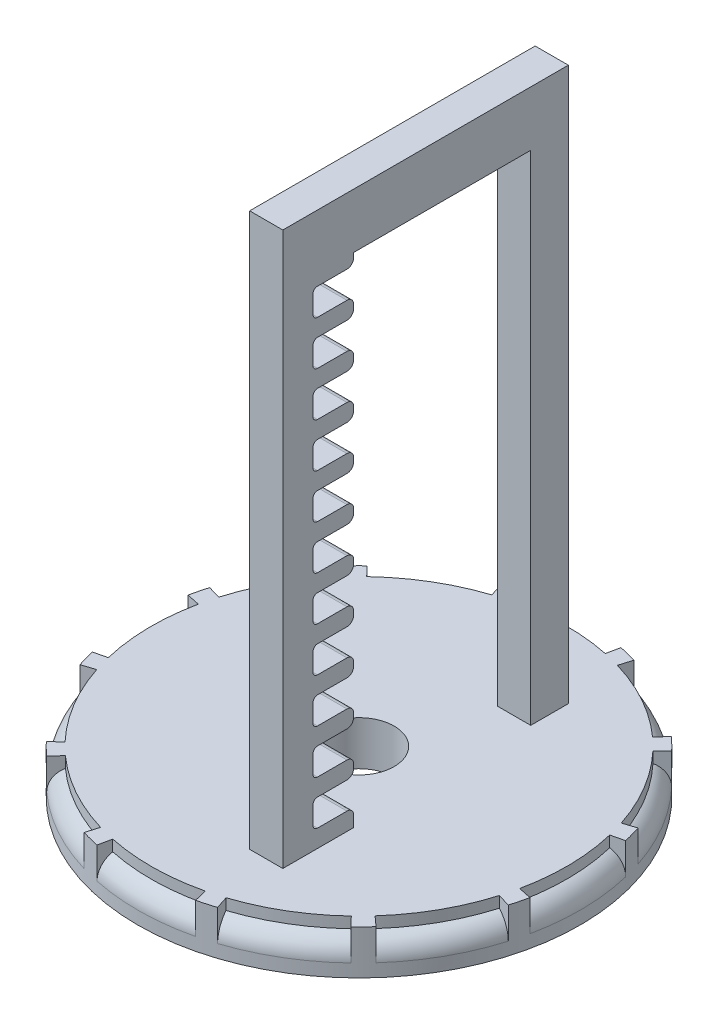
SolidWorks part; units mm, degrees
ref_plane "Front Plane" through (0, 0, 0) normal (0, 0, 1) x (1, 0, 0)
ref_plane "Top Plane" through (0, 0, 0) normal (0, 1, 0) x (1, 0, 0)
ref_plane "Right Plane" through (0, 0, 0) normal (1, 0, 0) x (0, 0, -1)
sketch "Sketch1" plane through (0, 0, 0) normal (0, 1, 0) x (1, 0, 0)
  circle A0 centre (0, 0) radius 100
  dimension "D1" = 200
extrude "Boss-Extrude1" add sketch "Sketch1" along normal blind 20
sketch "Sketch2" plane through (0, 20, 0) normal (0, 1, 0) x (1, 0, 0)
  line L0 (-23.3506, 97.2355) -> (-21.9496, 91.4014)
  line L2 (-1.4202, 99.9972) -> (0, 0) construction
  line L3 (19.345, 91.9879) -> (20.5798, 97.8594)
  line L4 (28.3956, 95.8837) -> (26.6918, 90.1307)
  line L5 (62.7472, 69.9913) -> (66.7524, 74.4589)
  line L6 (72.5331, 68.84) -> (68.1812, 64.7096)
  line L7 (89.3364, 29.2406) -> (95.0387, 31.1071)
  line L8 (97.2355, 23.3506) -> (91.4014, 21.9496)
  line L9 (91.9879, -19.345) -> (97.8594, -20.5798)
  line L10 (95.8837, -28.3956) -> (90.1307, -26.6918)
  line L11 (69.9913, -62.7472) -> (74.4589, -66.7524)
  line L12 (68.84, -72.5331) -> (64.7096, -68.1812)
  line L13 (29.2406, -89.3364) -> (31.1071, -95.0387)
  line L14 (23.3506, -97.2355) -> (21.9496, -91.4014)
  line L15 (-19.345, -91.9879) -> (-20.5798, -97.8594)
  line L16 (-28.3956, -95.8837) -> (-26.6918, -90.1307)
  line L17 (-62.7472, -69.9913) -> (-66.7524, -74.4589)
  line L18 (-72.5331, -68.84) -> (-68.1812, -64.7096)
  line L19 (-89.3364, -29.2406) -> (-95.0387, -31.1071)
  line L20 (-97.2355, -23.3506) -> (-91.4014, -21.9496)
  line L21 (-91.9879, 19.345) -> (-97.8594, 20.5798)
  line L22 (-95.8837, 28.3956) -> (-90.1307, 26.6918)
  line L23 (-69.9913, 62.7472) -> (-74.4589, 66.7524)
  line L24 (-68.84, 72.5331) -> (-64.7096, 68.1812)
  line L25 (-29.2406, 89.3364) -> (-31.1071, 95.0387)
  line L26 (0, 0) -> (-1.3349, 93.9905) construction
  circle A0 centre (0, 0) radius 100 construction
  arc A1 (-21.9496, 91.4014) -> (19.345, 91.9879) centre (0, 0) cw
  arc A3 (-23.3506, 97.2355) -> (20.5798, 97.8594) centre (0, 0) cw
  arc A4 (28.3956, 95.8837) -> (66.7524, 74.4589) centre (0, 0) cw
  arc A5 (26.6918, 90.1307) -> (62.7472, 69.9913) centre (0, 0) cw
  arc A6 (72.5331, 68.84) -> (95.0387, 31.1071) centre (0, 0) cw
  arc A7 (68.1812, 64.7096) -> (89.3364, 29.2406) centre (0, 0) cw
  arc A8 (97.2355, 23.3506) -> (97.8594, -20.5798) centre (0, 0) cw
  arc A9 (91.4014, 21.9496) -> (91.9879, -19.345) centre (0, 0) cw
  arc A10 (95.8837, -28.3956) -> (74.4589, -66.7524) centre (0, 0) cw
  arc A11 (90.1307, -26.6918) -> (69.9913, -62.7472) centre (0, 0) cw
  arc A12 (68.84, -72.5331) -> (31.1071, -95.0387) centre (0, 0) cw
  arc A13 (64.7096, -68.1812) -> (29.2406, -89.3364) centre (0, 0) cw
  arc A14 (23.3506, -97.2355) -> (-20.5798, -97.8594) centre (0, 0) cw
  arc A15 (21.9496, -91.4014) -> (-19.345, -91.9879) centre (0, 0) cw
  arc A16 (-28.3956, -95.8837) -> (-66.7524, -74.4589) centre (0, 0) cw
  arc A17 (-26.6918, -90.1307) -> (-62.7472, -69.9913) centre (0, 0) cw
  arc A18 (-72.5331, -68.84) -> (-95.0387, -31.1071) centre (0, 0) cw
  arc A19 (-68.1812, -64.7096) -> (-89.3364, -29.2406) centre (0, 0) cw
  arc A20 (-97.2355, -23.3506) -> (-97.8594, 20.5798) centre (0, 0) cw
  arc A21 (-91.4014, -21.9496) -> (-91.9879, 19.345) centre (0, 0) cw
  arc A22 (-95.8837, 28.3956) -> (-74.4589, 66.7524) centre (0, 0) cw
  arc A23 (-90.1307, 26.6918) -> (-69.9913, 62.7472) centre (0, 0) cw
  arc A24 (-68.84, 72.5331) -> (-31.1071, 95.0387) centre (0, 0) cw
  arc A25 (-64.7096, 68.1812) -> (-29.2406, 89.3364) centre (0, 0) cw
  point P56 (0, 0)
  dimension "D1" = 94
  dimension "D2" = 22
  dimension "D3" = 12
extrude "Cut-Extrude1" cut sketch "Sketch2" against normal blind 5
fillet "Fillet1" radius 10 12 edges at (-51.2248, 15, -85.8838) (-87.3038, 15, -48.7651) (-99.9899, 15, 1.4201) (-85.8838, 15, 51.2248) (-48.7651, 15, 87.3038) (1.4201, 15, 99.9899) (51.2248, 15, 85.8838) (87.3038, 15, 48.7651) (99.9899, 15, -1.4201) (85.8838, 15, -51.2248) (48.7651, 15, -87.3038) (-1.4201, 15, -99.9899)
sketch "Sketch7" plane through (0, 20, 0) normal (0, 1, 0) x (1, 0, 0)
  line L0 (0.0235, 93.9705) -> (-1.4347, 94.0321) construction
sketch "Sketch8" plane through (0, 20, 0) normal (0, 1, 0) x (1, 0, 0)
  line L0 (-1.4347, 94.0321) -> (1.3349, -93.9905) construction
  line L1 (15.6192, 64.0208) -> (15.6192, 47.0208)
  line L2 (15.6192, 64.0208) -> (30.6192, 64.0208)
  line L3 (15.6192, 47.0208) -> (30.6192, 47.0208)
  line L4 (30.6192, 64.0208) -> (30.6192, 47.0208)
  line L5 (15.6192, -33.0513) -> (30.6192, -33.0513)
  line L6 (30.6192, -65.0513) -> (30.6192, -33.0513)
  line L7 (15.6192, -65.0513) -> (30.6192, -65.0513)
  line L8 (15.6192, -65.0513) -> (15.6192, -33.0513)
  arc A0 (-19.345, -91.9879) -> (21.9496, -91.4014) centre (0, 0) ccw construction
  point P0 (-0.0499, 0.0208)
  dimension "D1" = 15.1803
  dimension "D2" = 15
  dimension "D3" = 17
  dimension "D4" = 64
  dimension "D5" = 32
extrude "Boss-Extrude5" add sketch "Sketch8" along normal blind 250
sketch "Sketch9" plane through (30.6192, 0, 0) normal (1, 0, 0) x (0, 0, -1)
  line L0 (-33.0513, 20) -> (-33.0513, 24.9833)
  line L1 (-33.0513, 270) -> (-33.0513, 20) construction
  line L2 (-51.4069, 29.9833) -> (-51.4069, 38.1448)
  line L3 (-49.4069, 40.1448) -> (-36.0513, 40.1448)
  line L4 (-49.4069, 27.9833) -> (-36.0513, 27.9833)
  line L5 (-33.0513, 24.9833) -> (-33.0513, 43.1448)
  line L6 (-33.0513, 43.1448) -> (-33.0513, 24.9833)
  arc A0 (-33.0513, 24.9833) -> (-36.0513, 27.9833) centre (-36.0513, 24.9833) ccw
  arc A1 (-36.0513, 40.1448) -> (-33.0513, 43.1448) centre (-36.0513, 43.1448) ccw
  arc A2 (-49.4069, 27.9833) -> (-51.4069, 29.9833) centre (-49.4069, 29.9833) cw
  arc A3 (-49.4069, 40.1448) -> (-51.4069, 38.1448) centre (-49.4069, 38.1448) ccw
  dimension "D1" = 2
  dimension "D2" = 2
  dimension "D4" = 3
  dimension "D5" = 3
  dimension "D3" = 12.1616
extrude "Cut-Extrude2" cut sketch "Sketch9" against normal up to next contours L5 A1 L3 A3 L2 A2 L4 A0
pattern_linear "LPattern1" count 12 spacing 20 along (0, 1, 0) of "Cut-Extrude2"
sketch "Sketch13" plane through (0, 0, -64.0208) normal (0, 0, -1) x (-1, 0, 0)
  line L0 (-15.6192, 270) -> (-15.6192, 20) construction
  line L1 (-30.6192, 270) -> (-15.6192, 270)
  line L2 (-30.6192, 270) -> (-30.6192, 245.1786)
  line L3 (-30.6192, 245.1786) -> (-15.6192, 245.1786)
  line L4 (-15.6192, 270) -> (-15.6192, 245.1786)
extrude "Boss-Extrude7" add sketch "Sketch13" against normal up to surface (129.0721 mm away) up to face at (23.1192, 145, 65.0513)
sketch "Sketch14" plane through (0, 20, 0) normal (0, 1, 0) x (1, 0, 0)
  circle A0 centre (0, 0) radius 15.8904
  dimension "D1" = 31.7808
extrude "Cut-Extrude3" cut sketch "Sketch14" against normal through all
